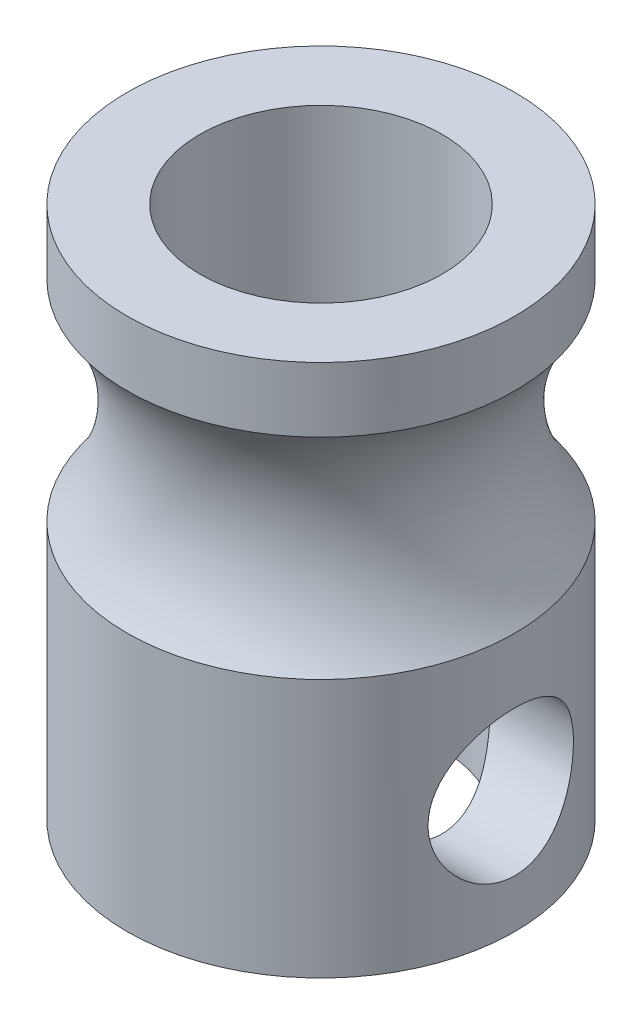
SolidWorks part; units mm, degrees
ref_plane "Alzado" through (0, 0, 0) normal (0, 0, 1) x (1, 0, 0)
ref_plane "Planta" through (0, 0, 0) normal (0, 1, 0) x (1, 0, 0)
ref_plane "Vista lateral" through (0, 0, 0) normal (1, 0, 0) x (0, 0, -1)
sketch "Croquis1" plane through (0, 0, 0) normal (0, 1, 0) x (1, 0, 0)
  circle A0 centre (0, 0) radius 4
  circle A1 centre (0, 0) radius 2.5
  dimension "D1" = 8
  dimension "D2" = 5
extrude "Saliente-Extruir1" add sketch "Croquis1" along normal blind 11
ref_plane "Plano1" through (4, 0, 0) normal (1, 0, 0) x (0, 0, -1)
sketch "Croquis2" plane through (4, 0, 0) normal (1, 0, 0) x (0, 0, -1)
  line L0 (-4, 0) -> (4, 0) construction
  circle A0 centre (0, 2.5) radius 1.5
  dimension "D3" = 3
  dimension "D1" = 2.5
  dimension "D2" = 4
extrude "Cortar-Extruir2" cut sketch "Croquis2" against normal blind 2
sketch "Croquis3" plane through (0, 0, 0) normal (0, 0, 1) x (1, 0, 0)
  line L0 (-4, 0) -> (4, 0) construction
  line L1 (0, 0) -> (0, 11) construction
  line L2 (2.5, 11) -> (-2.5, 11) construction
  circle A0 centre (6.75, 7.5) radius 3.5
  circle A1 centre (-6.75, 7.5) radius 3
  dimension "D4" = 6
  dimension "D5" = 7
  dimension "D1" = 7.5
  dimension "D2" = 6.75
  dimension "D3" = 6.75
ref_axis "Eje1" through (0, 11, 0) along (0, -1, 0)
revolve "Cortar-Revolución2" cut sketch "Croquis3" angle 360 about L1
